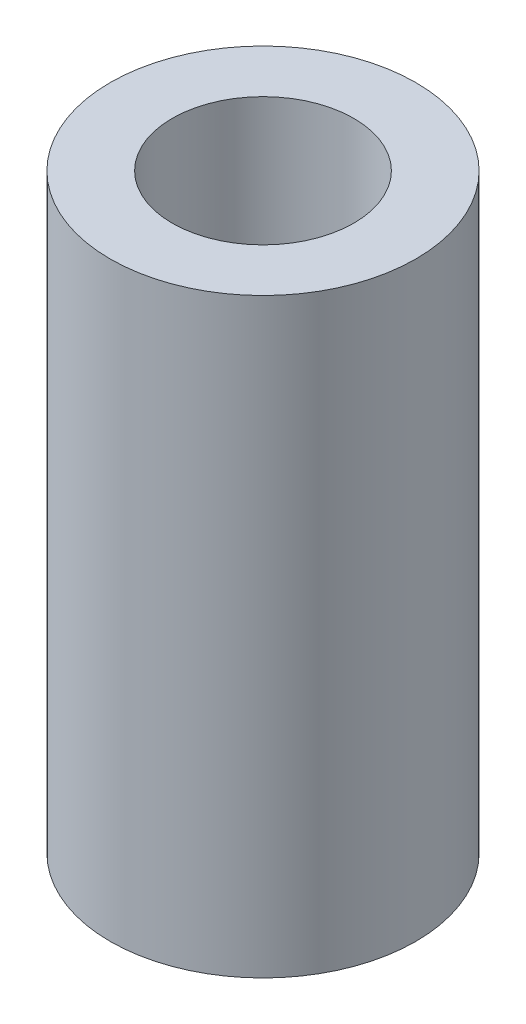
SolidWorks part; units mm, degrees
material "Rubber"
ref_plane "Front Plane" through (0, 0, 0) normal (0, 0, 1) x (1, 0, 0)
ref_plane "Top Plane" through (0, 0, 0) normal (0, 1, 0) x (1, 0, 0)
ref_plane "Right Plane" through (0, 0, 0) normal (1, 0, 0) x (0, 0, -1)
sketch "Sketch1" plane through (0, 0, 0) normal (0, 0, 1) x (1, 0, 0)
  line L0 (0, 0) -> (0, 52.07)
  dimension "D1" = 52.07
sweep "Sweep1" add path "Sketch1" circular profile diameter 26.924 parameters "D3"=26.924
sweep "Cut-Sweep1" cut path "Sketch1<2>" circular profile diameter 16.002 parameters "D3"=16.002
sketch "Sketch1<2>" plane through (0, 0, 0) normal (0, 0, 1) x (1, 0, 0) same geometry as "Sketch1"
